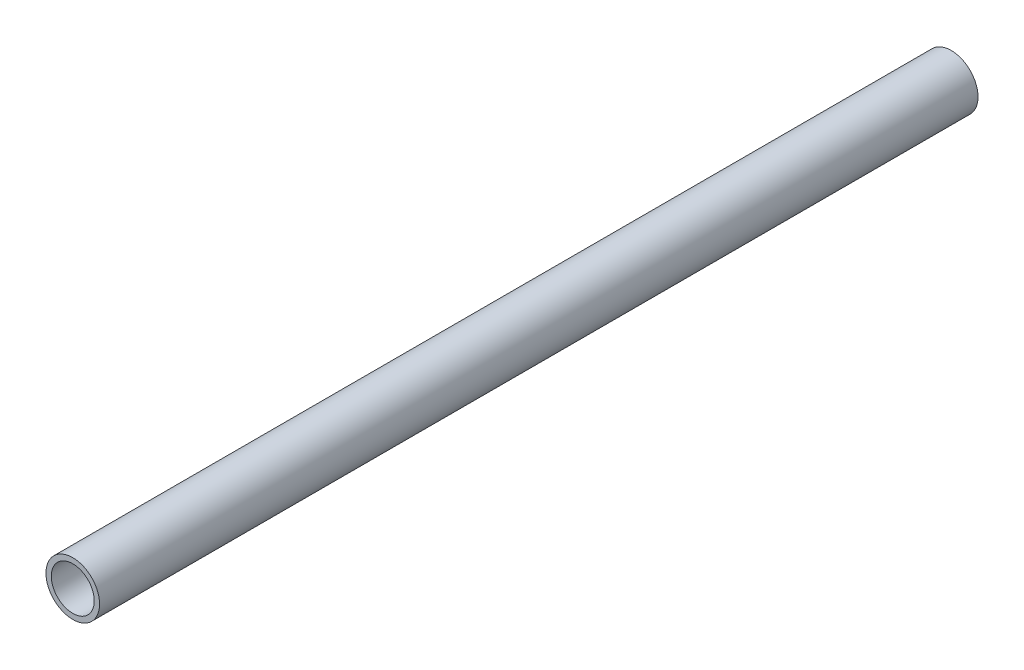
SolidWorks part; units mm, degrees
ref_plane "Front Plane" through (0, 0, 0) normal (0, 0, 1) x (1, 0, 0)
ref_plane "Top Plane" through (0, 0, 0) normal (0, 1, 0) x (1, 0, 0)
ref_plane "Right Plane" through (0, 0, 0) normal (1, 0, 0) x (0, 0, -1)
sketch "Sketch1" plane through (0, 0, 0) normal (0, 0, 1) x (1, 0, 0)
  circle A0 centre (0, 0) radius 4.05
  dimension "D1" = 8.1
extrude "Extrude-Thin1" add sketch "Sketch1" along normal blind 165.5 thin thin type one direction wall 1
